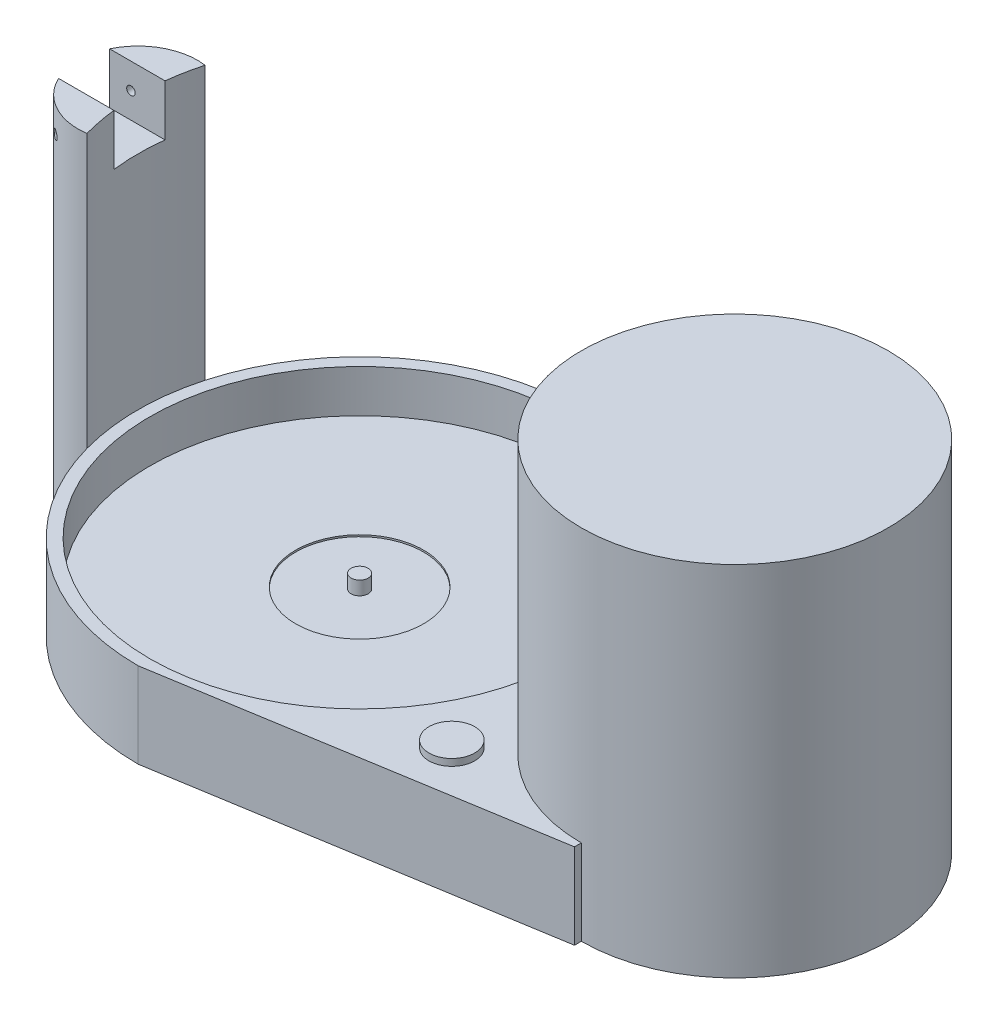
SolidWorks part; units mm, degrees
material "ABS"
ref_plane "Front Plane" through (0, 0, 0) normal (0, 0, 1) x (1, 0, 0)
ref_plane "Top Plane" through (0, 0, 0) normal (0, 1, 0) x (1, 0, 0)
ref_plane "Right Plane" through (0, 0, 0) normal (1, 0, 0) x (0, 0, -1)
sketch "Sketch3" plane through (0, 0, 0) normal (0, 1, 0) x (1, 0, 0)
  line L0 (0, -3344.3672) -> (0, 163873.9925) construction
  line L1 (-3344.3672, 0) -> (163873.9925, 0) construction
  line L2 (0, -130) -> (220, -94)
  line L3 (220, -94) -> (220, -90)
  line L4 (0, 130) -> (220, 94)
  line L5 (220, 94) -> (220, 90)
  arc A0 (0, 130) -> (0, -130) centre (0, 0) ccw
  circle A1 centre (220, 0) radius 90
  arc A2 (-125.2885, 34.6814) -> (-125.2885, -34.6814) centre (-130, 0) ccw
  dimension "D1" = 260
  dimension "D2" = 180
  dimension "D6" = 35
  dimension "D3" = 220
  dimension "D4" = 4
  dimension "D5" = 4
extrude "Boss-Extrude1" add sketch "Sketch3" along normal blind 210 contours A1 L2 region at (220, 0, 0)
extrude "Boss-Extrude2" add sketch "Sketch3<3>" along normal blind 50 contours A1 L5 L4 A0 L2 L3 region at (21.4344, 0, 0)
sketch "Sketch3<3>" plane through (0, 0, 0) normal (0, 1, 0) x (1, 0, 0) same geometry as "Sketch3"
extrude "Boss-Extrude3" add sketch "Sketch3<4>" along normal blind 210 contours A0 A2 region at (-143.9736, 0, 0)
sketch "Sketch3<4>" plane through (0, 0, 0) normal (0, 1, 0) x (1, 0, 0) same geometry as "Sketch3"
sketch "Sketch4" plane through (0, 50, 0) normal (0, 1, 0) x (1, 0, 0)
  circle A0 centre (0, 0) radius 123
  dimension "D1" = 246
extrude "Cut-Extrude1" cut sketch "Sketch4" against normal blind 25
sketch "Sketch6" plane through (0, 210, 0) normal (0, 1, 0) x (1, 0, 0)
  line L0 (-161.6228, 15) -> (-129.1317, 15)
  line L1 (-161.6228, -15) -> (-129.1317, -15)
  line L2 (-180.6344, 0) -> (-107.0266, 0) construction
  arc A0 (-125.2885, 34.6814) -> (-125.2885, -34.6814) centre (-130, 0) ccw construction
  arc A1 (-125.2885, 34.6814) -> (-125.2885, -34.6814) centre (0, 0) ccw construction
  arc A2 (-125.2885, 34.6814) -> (-125.2885, -34.6814) centre (0, 0) ccw construction
  arc A3 (-161.6228, 15) -> (-161.6228, -15) centre (-130, 0) ccw
  arc A4 (-129.1317, 15) -> (-129.1317, -15) centre (0, 0) ccw
  dimension "D1" = 30
  dimension "D2" = 15
extrude "Cut-Extrude2" cut sketch "Sketch6" against normal blind 30
sketch "Sketch8" plane through (0, 0, 15) normal (0, 0, -1) x (-1, 0, 0)
  line L0 (145.3772, 210) -> (145.3772, 180) construction
  line L1 (161.6228, 210) -> (129.1317, 210) construction
  line L2 (161.6228, 180) -> (129.1317, 180) construction
  line L3 (129.1317, 195) -> (161.6228, 195) construction
  line L4 (129.1317, 180) -> (129.1317, 210) construction
  line L5 (161.6228, 180) -> (161.6228, 210) construction
  circle A0 centre (149.1317, 195) radius 2.5
  dimension "D1" = 5
  dimension "D2" = 15
  dimension "D3" = 20
extrude "Cut-Extrude3" cut sketch "Sketch8" against normal through all both and the other way through all
sketch "Sketch9" plane through (0, 25, 0) normal (0, 1, 0) x (1, 0, 0)
  circle A0 centre (0, 0) radius 37.5
  dimension "D1" = 75
extrude "Cut-Extrude4" cut sketch "Sketch9" against normal blind 1
sketch "Sketch10" plane through (0, 24, 0) normal (0, 1, 0) x (1, 0, 0)
  circle A0 centre (0, 0) radius 5
  dimension "D1" = 10
extrude "Boss-Extrude4" add sketch "Sketch10" along normal blind 8
sketch "Sketch11" plane through (0, 50, 0) normal (0, 1, 0) x (1, 0, 0)
  circle A0 centre (133.691, -79.6251) radius 13.4018
extrude "Boss-Extrude5" add sketch "Sketch11" along normal blind 4
